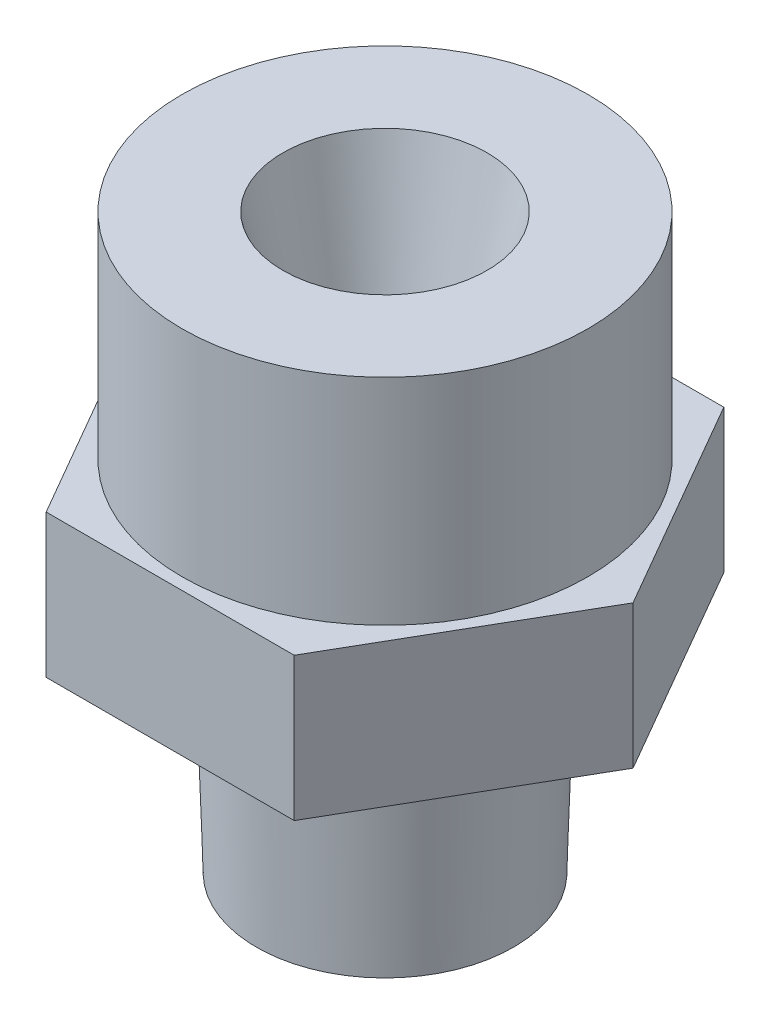
SolidWorks part; units mm, degrees
material "AISI 316 Annealed Stainless Steel Bar (SS)"
ref_plane "Front Plane" through (0, 0, 0) normal (0, 0, 1) x (1, 0, 0)
ref_plane "Top Plane" through (0, 0, 0) normal (0, 1, 0) x (1, 0, 0)
ref_plane "Right Plane" through (0, 0, 0) normal (1, 0, 0) x (0, 0, -1)
sketch "Sketch1" plane through (0, 0, 0) normal (0, 1, 0) x (1, 0, 0)
  circle A1 centre (0, 0) radius 9
  dimension "D2" = 18
extrude "Boss-Extrude1" add sketch "Sketch1" along normal blind 9.525
sketch "Sketch4" plane through (0, 0, 0) normal (0, -1, 0) x (1, 0, 0)
  circle A0 centre (0, 0) radius 3.175
  dimension "D1" = 6.35
extrude "Cut-Extrude1" cut sketch "Sketch4" against normal blind 3.175
sketch "Sketch5" plane through (0, 3.175, 0) normal (0, -1, 0) x (-1, 0, 0)
  circle A0 centre (0, 0) radius 3.175
  circle A1 centre (0, 0) radius 3.175 construction
extrude "Cut-Extrude2" cut sketch "Sketch5" against normal through all draft 12 draft outward yes
sketch "Sketch6" plane through (0, 0, 0) normal (0, -1, 0) x (1, 0, 0)
  line L1 (-10.9985, 0) -> (-5.4993, -9.525)
  line L2 (-5.4993, -9.525) -> (5.4993, -9.525)
  line L3 (5.4993, -9.525) -> (10.9985, 0)
  line L4 (10.9985, 0) -> (5.4993, 9.525)
  line L5 (5.4993, 9.525) -> (-5.4993, 9.525)
  line L6 (-5.4993, 9.525) -> (-10.9985, 0)
  circle A0 centre (0, 0) radius 9.525 construction
  circle A1 centre (0, 0) radius 3.175
  circle A2 centre (0, 0) radius 3.175 construction
  dimension "D1" = 19.05
extrude "Boss-Extrude3" add sketch "Sketch6" along normal blind 6.35
sketch "Sketch7" plane through (0, -6.35, 0) normal (0, -1, 0) x (1, 0, 0)
  circle A3 centre (0, 0) radius 6
  dimension "D1" = 12
extrude "Boss-Extrude4" add sketch "Sketch7" along normal blind 9.525 draft 1.79
sketch "Sketch8" plane through (0, -15.875, 0) normal (0, -1, 0) x (1, 0, 0)
  circle A0 centre (0, 0) radius 3.175
  dimension "D1" = 6.35
extrude "Cut-Extrude3" cut sketch "Sketch8" against normal through all
